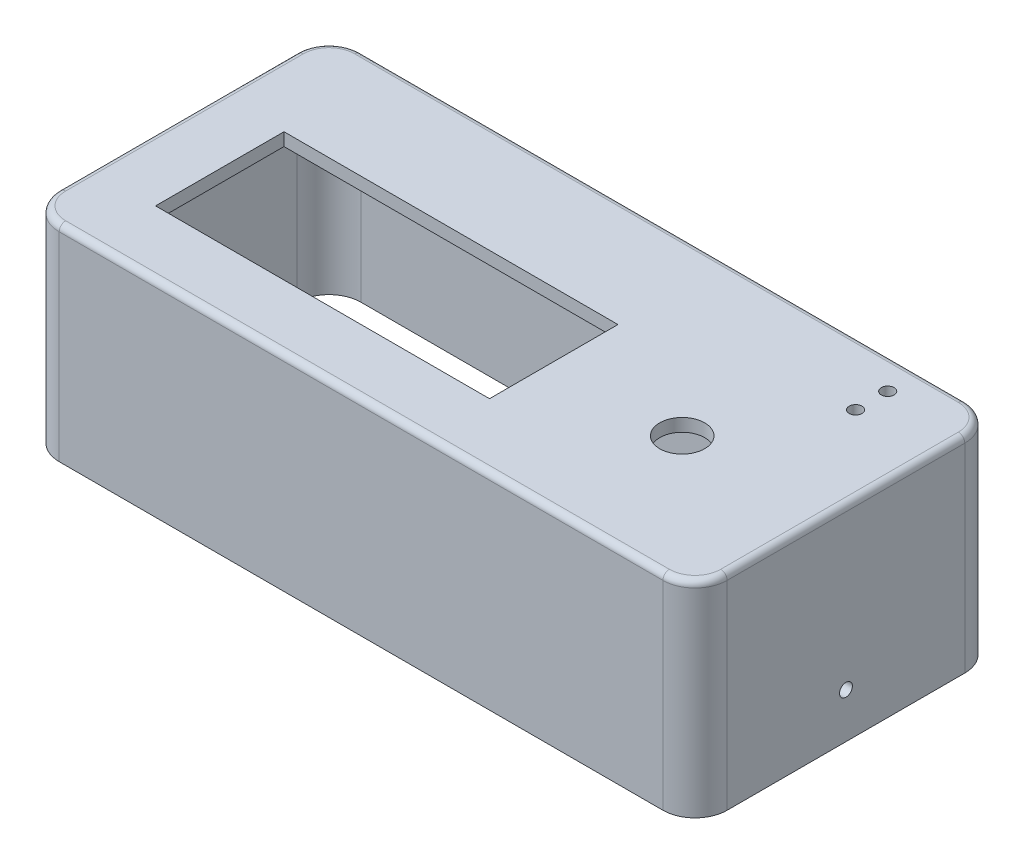
SolidWorks part; units mm, degrees
ref_plane "Спереди" through (0, 0, 0) normal (0, 0, 1) x (1, 0, 0)
ref_plane "Сверху" through (0, 0, 0) normal (0, 1, 0) x (1, 0, 0)
ref_plane "Справа" through (0, 0, 0) normal (1, 0, 0) x (0, 0, -1)
sketch "Эскиз1" plane through (0, 0, 0) normal (0, 1, 0) x (1, 0, 0)
  line L0 (-52.1831, 0) -> (84.9577, 0) construction
  line L1 (26, -10) -> (-26, -10)
  line L2 (26, -10) -> (26, 10)
  line L3 (26, 10) -> (-26, 10)
  line L4 (-26, -10) -> (-26, 10)
  line L5 (26, -10) -> (-26, 10) construction
  line L6 (26, 10) -> (-26, -10) construction
  line L7 (-29, 25) -> (61, 25)
  line L8 (-34, 20) -> (-34, -13)
  line L9 (-29, -18) -> (61, -18)
  line L10 (66, 20) -> (66, -13)
  line L11 (56, 22) -> (56, 17) construction
  line L12 (-31, 27) -> (63, 27)
  line L13 (-36, 22) -> (-36, -15)
  line L14 (-31, -20) -> (63, -20)
  line L15 (68, 22) -> (68, -15)
  circle A0 centre (46, 0) radius 3.5
  circle A1 centre (46, 0) radius 8.5
  arc A2 (-36, -15) -> (-31, -20) centre (-31, -15) ccw
  arc A3 (-34, -13) -> (-29, -18) centre (-29, -13) ccw
  arc A4 (68, -15) -> (63, -20) centre (63, -15) cw
  arc A5 (66, -13) -> (61, -18) centre (61, -13) cw
  arc A6 (68, 22) -> (63, 27) centre (63, 22) ccw
  arc A7 (66, 20) -> (61, 25) centre (61, 20) ccw
  arc A8 (-36, 22) -> (-31, 27) centre (-31, 22) cw
  arc A9 (-29, 25) -> (-34, 20) centre (-29, 20) ccw
  circle A10 centre (56, 22) radius 1
  circle A11 centre (56, 17) radius 1
  point P0 (0, 0)
  dimension "D5" = 8
  dimension "D6" = 7
  dimension "D7" = 17
  dimension "D9" = 20
  dimension "D14" = 5
  dimension "D15" = 5
  dimension "D16" = 2
  dimension "D1" = 52
  dimension "D2" = 20
  dimension "D3" = 8
  dimension "D4" = 15
  dimension "D8" = 20
  dimension "D10" = 2
  dimension "D11" = 2
  dimension "D12" = 2
  dimension "D13" = 2
  dimension "D17" = 3
  dimension "D18" = 10
extrude "Бобышка-Вытянуть1" add sketch "Эскиз1" against normal blind 2 contours L10 L7 L8 L9 A1 L1 L4 L3 L2 | A1 A0 region at (16, 0, -23.9115) region at (37.7404, 0, 0)
extrude "Бобышка-Вытянуть2" add sketch "Эскиз1<3>" against normal blind 32 contours L15 L12 L13 L14 L7 L10 L9 L8 region at (16, 0, -25.8587)
sketch "Эскиз1<3>" plane through (0, 0, 0) normal (0, 1, 0) x (1, 0, 0) same geometry as "Эскиз1"
fillet "Скругление2" radius 1 8 edges at (68, 0, -3.5) (16, 0, -27) (-36, 0, -3.5) (16, 0, 20) (-34.5355, 0, 18.5355) (-34.5355, 0, -25.5355) (66.5355, 0, -25.5355) (66.5355, 0, 18.5355)
sketch "Эскиз2" plane through (68, 0, 0) normal (1, 0, 0) x (0, 0, -1)
  line L0 (3.5, -32) -> (3.5, -12.1784) construction
  line L1 (22, -32) -> (-15, -32) construction
  circle A0 centre (3.5, -25) radius 1
  dimension "D1" = 2
  dimension "D2" = 7
extrude "Вырез-Вытянуть1" cut sketch "Эскиз2" against normal through all both and the other way through all
sketch "Эскиз3" plane through (0, 0, -25) normal (0, 0, 1) x (1, 0, 0)
  line L1 (61, -32) -> (49, -32)
  line L2 (61, -32) -> (61, -22)
  line L3 (61, -22) -> (49, -22)
  line L4 (49, -32) -> (49, -22)
  line L5 (61, -32) -> (61, -2) construction
  line L6 (61, -32) -> (61, -2)
  line M5 (-29, -32) -> (61, -32)
  line M6 (61, -32) -> (61, -2)
  dimension "D1" = 10
  dimension "D2" = 12
extrude "Вырез-Вытянуть2" cut sketch "Эскиз3" against normal blind 10 contours L4 L3 M5 M6 region at (55, -27, -25)
